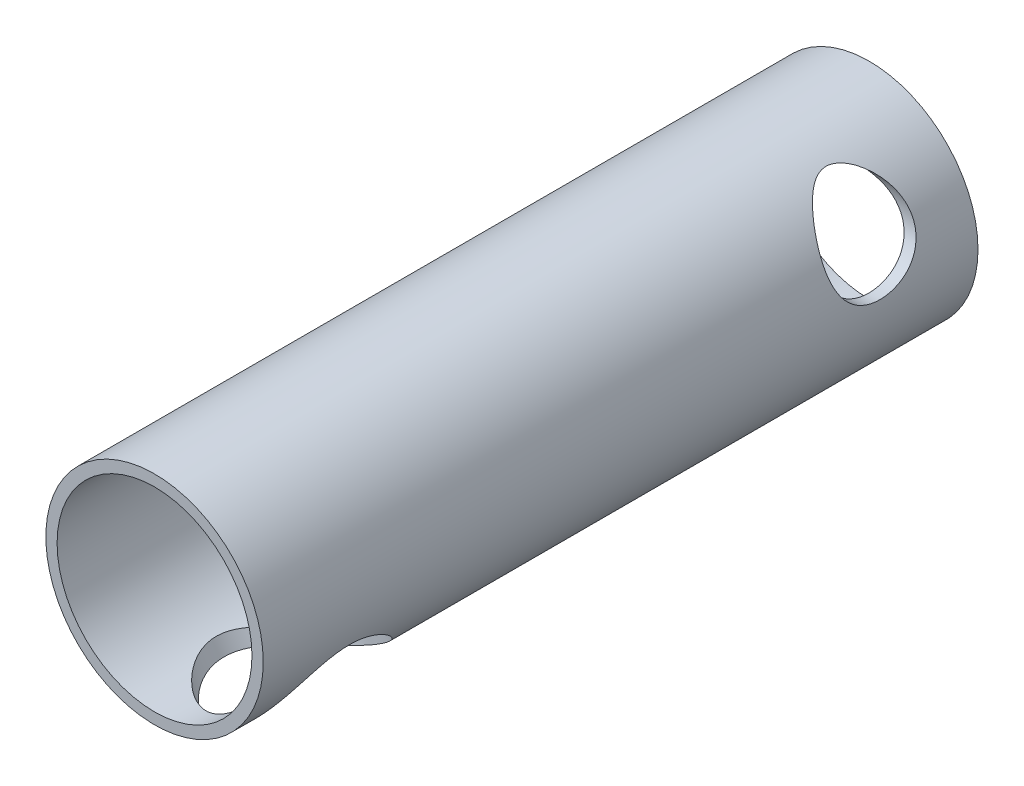
SolidWorks part; units mm, degrees
ref_plane "Front Plane" through (0, 0, 0) normal (0, 0, 1) x (1, 0, 0)
ref_plane "Top Plane" through (0, 0, 0) normal (0, 1, 0) x (1, 0, 0)
ref_plane "Right Plane" through (0, 0, 0) normal (1, 0, 0) x (0, 0, -1)
sketch "Sketch1" plane through (0, 0, 0) normal (0, 0, 1) x (1, 0, 0)
  line L0 (-0.0494, 0) -> (-22.2407, -0.9122)
  circle A0 centre (-0.0494, 0) radius 22.21
  circle A1 centre (-0.0494, 0) radius 19.91
  point P4 (-13.1198, -17.9569)
  dimension "D1" = 44.42
  dimension "D2" = 39.82
extrude "Boss-Extrude1" add sketch "Sketch1" along normal blind 146.05 contours A1 A0 | A0 | A1 region at (-0.4927, 21.5773, 0)
sketch "Sketch2" plane through (0, 0, 146.05) normal (0, 0, 1) x (1, 0, 0)
  line L0 (0, 0) -> (11.0926, -19.213)
  line L1 (0, 0) -> (22.1606, 0)
  circle A1 centre (-0.0494, 0) radius 22.21 construction
  dimension "D1" = 60
ref_plane "Plane1" through (11.0926, -19.213, 146.05) normal (0.5017, -0.8651, 0) x (-0.8651, -0.5017, 0)
ref_plane "Plane2" through (22.1606, 0, 146.05) normal (1, 0, 0) x (0, 0, -1)
sketch "Sketch4" plane through (22.1606, 0, 146.05) normal (1, 0, 0) x (0, 0, -1)
  line L0 (146.05, -22.21) -> (146.05, 22.21) construction
  line L1 (146.05, 22.21) -> (0, 22.21) construction
  circle A0 centre (126.05, 10.1535) radius 9.0424
  dimension "D1" = 18.0848
  dimension "D2" = 20
  dimension "D3" = 12.0565
sketch "Sketch5" plane through (11.0926, -19.213, 146.05) normal (0.5017, -0.8651, 0) x (-0.8651, -0.5017, 0)
  line L0 (-0.0428, 0) -> (-19.213, 0) construction
  circle A0 centre (-0.0494, 18.7) radius 14.8463
  dimension "D1" = 29.6926
  dimension "D2" = 18.7
extrude "Cut-Extrude2" cut sketch "Sketch5" against normal up to next contours A0
extrude "Cut-Extrude3" cut sketch "Sketch4" against normal up to next contours A0
equation "\"can_outer_diameter\"= 44.42mm"
equation "\"D1@Sketch1\"=\"can_outer_diameter\""
equation "\"can_thickness\"= 2.3"
equation "\"D2@Sketch1\"=\"can_outer_diameter\"-2*\"can_thickness\""
equation "\"can_height\"= 5.75in"
equation "\"D1@Boss-Extrude1\"=\"can_height\""
equation "\"inlet_diameter\"= 0.712in"
equation "\"D1@Sketch4\"=\"inlet_diameter\""
equation "\"outlet_diameter\"= 1.169in"
equation "\"D1@Sketch5\"=\"outlet_diameter\""
equation "\"D2@Sketch5\"=6mm+12.7"
equation "\"D3@Sketch4\"=\"inlet_diameter\"/1.5"
